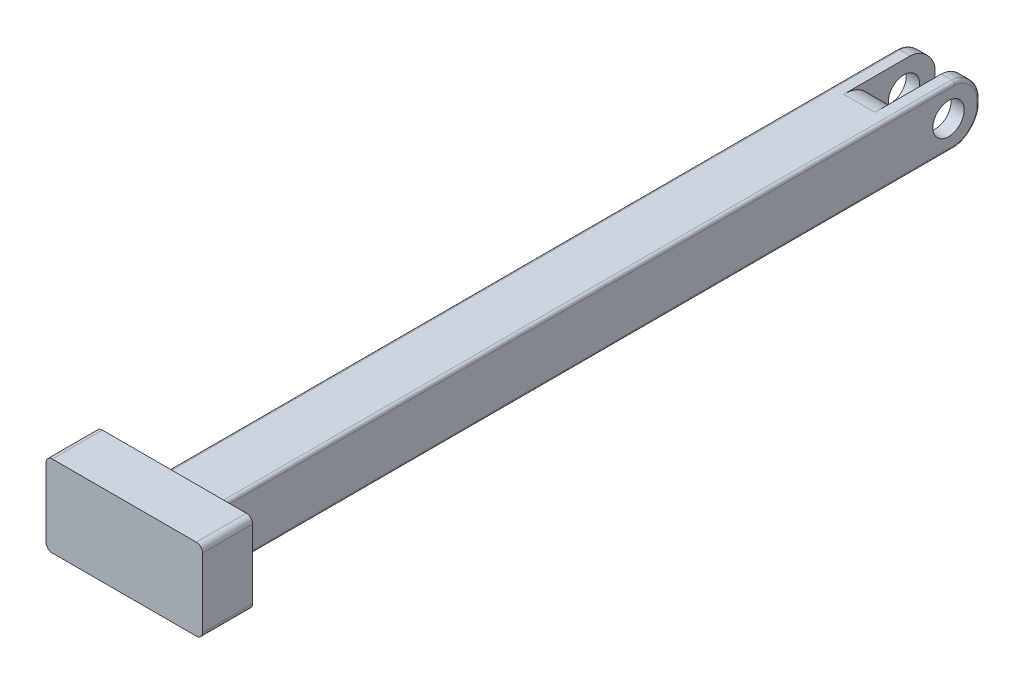
SolidWorks part; units mm, degrees
ref_plane "Alzado" through (0, 0, 0) normal (1, 0, 0) x (0, 1, 0)
ref_plane "Planta" through (0, 0, 0) normal (0, 0, 1) x (0, 1, 0)
ref_plane "Vista lateral" through (0, 0, 0) normal (0, 1, 0) x (-1, 0, 0)
sketch "Croquis1" plane through (0, 0, 0) normal (1, 0, 0) x (0, 1, 0)
  line L0 (-4.625, 132) -> (-4.625, 0)
  line L1 (-4.625, 132) -> (4.625, 132)
  line L2 (-4.625, 0) -> (4.625, 0)
  line L3 (4.625, 124) -> (4.625, 0)
  line L4 (-4.625, 132) -> (4.625, 0) construction
  line L5 (-4.625, 0) -> (4.625, 132) construction
  line L6 (4.625, 124) -> (-4.625, 124)
  line L7 (4.625, 132) -> (8.375, 132)
  line L9 (4.625, 124) -> (8.375, 124)
  line L10 (8.375, 132) -> (8.375, 124)
  line L12 (4.625, 0) -> (-4.625, 0)
  line L13 (4.625, 0) -> (4.625, 10)
  line L14 (4.625, 10) -> (-4.625, 10)
  line L15 (-4.625, 0) -> (-4.625, 10)
  circle A0 centre (0, 5) radius 2.5
  point P0 (0, 0)
  point P1 (0, 66)
  dimension "D6" = 5
  dimension "D1" = 9.25
  dimension "D3" = 8
  dimension "D4" = 13
  dimension "D5" = 10
  dimension "D7" = 5
  dimension "D2" = 119
extrude "Saliente-Extruir1" add sketch "Croquis1" along normal mid plane 9.25 contours L3 L6 L0 L2 | L3 L14 L0 L2 A0 region at (0, 0, 67) region at (0, 0, 9.8638)
extrude "Saliente-Extruir2" add sketch "Croquis1<3>" along normal mid plane 25 contours L10 L7 L1 L0 L6 L9 region at (0, 1.875, 128)
sketch "Croquis1<3>" plane through (0, 0, 0) normal (1, 0, 0) x (0, 1, 0) same geometry as "Croquis1"
extrude "Cortar-Extruir1" cut sketch "Croquis1<4>" against normal mid plane 5 contours L3 L14 L0 L2 A0 region at (0, 0, 9.8638)
sketch "Croquis1<4>" plane through (0, 0, 0) normal (1, 0, 0) x (0, 1, 0) same geometry as "Croquis1"
fillet "Redondeo1" radius 4 2 edges at (3.5625, -4.625, 0) (3.5625, 4.625, 0) conic radius 5
fillet "Redondeo2" radius 4.625 2 edges at (0, 4.625, 10) (0, -4.625, 10) conic radius 4
fillet "Redondeo3" radius 0.5 10 edges
fillet "Redondeo4" radius 1 4 edges at (-12.5, -4.625, 128) (-12.5, 8.375, 128) (12.5, 8.375, 128) (12.5, -4.625, 128)
equation "\"D7@Croquis1\"=\"D5@Croquis1\"/2"
